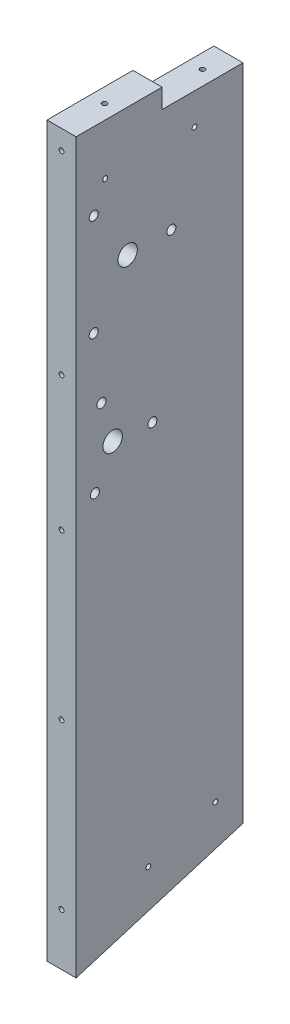
SolidWorks part; units mm, degrees
material "Beech"
ref_plane "Front Plane" through (0, 0, 0) normal (0, 0, 1) x (1, 0, 0)
ref_plane "Top Plane" through (0, 0, 0) normal (0, 1, 0) x (1, 0, 0)
ref_plane "Right Plane" through (0, 0, 0) normal (1, 0, 0) x (0, 0, -1)
sketch "Sketch1" plane through (0, 0, 0) normal (0, 0, 1) x (1, 0, 0)
  line L0 (-331.7795, -427.3421) -> (-331.7795, 0) construction
  line L1 (93.2955, -427.3421) -> (-341.3045, -427.3421) construction
  line L3 (-322.2545, -427.3421) -> (-322.2545, 0)
  line L4 (-341.3045, -427.3421) -> (-341.3045, 0)
  line L5 (-322.2545, -427.3421) -> (-341.3045, -427.3421)
  line L6 (-322.2545, 0) -> (-341.3045, 0)
  line L7 (-341.3045, -427.3421) -> (-341.3045, 12.7) construction
  line L8 (-331.7795, -427.3421) -> (-331.7795, 0) construction
  dimension "D1" = 19.05
extrude "Boss-Extrude1" add sketch "Sketch1" along normal up to surface (53 mm away)
sketch "Sketch2" plane through (0, 0, 53) normal (0, 0, 1) x (1, 0, 0)
  line L0 (-231.3045, 12.7) -> (-341.3045, 12.7) construction
  line L1 (-322.2545, 12.7) -> (-341.3045, 12.7)
  line L4 (-341.3045, 0) -> (-341.3045, -427.3421)
  line L5 (-341.3045, -427.3421) -> (-322.2545, -427.3421)
  line L6 (-322.2545, -427.3421) -> (-322.2545, 0)
  line L7 (-322.2545, 0) -> (-341.3045, 0)
  line L8 (-341.3045, 12.7) -> (-341.3045, -427.3421)
  line L9 (-341.3045, -427.3421) -> (-322.2545, -427.3421)
  line L10 (-322.2545, -427.3421) -> (-322.2545, 12.7)
  dimension "D1" = 0
extrude "Boss-Extrude2" add sketch "Sketch2" along normal up to surface (56.3 mm away)
sketch "Sketch3" plane through (-341.3045, 0, 0) normal (-1, 0, 0) x (0, 0, 1)
  line L0 (0, -427.3421) -> (109.3, -427.3421)
  line L1 (109.3, -427.3421) -> (109.3, -464.2661)
  line L2 (109.3, -464.2661) -> (0, -431.1858)
  line L3 (-12.7, -427.3421) -> (522.1409, -589.2145) construction
  line L4 (0, -431.1858) -> (0, -427.3421)
extrude "Boss-Extrude3" add sketch "Sketch3" against normal through all
hole_wizard "15/64 (0.23438) Diameter Hole1" positions "Sketch5" profile "Sketch6" hole size "15/64" standard "ANSI Inch" end condition through all
sketch "Sketch5" plane through (-341.3045, 0, 0) normal (-1, 0, 0) x (0, 0, 1)
  point P0 (97.7483, -37.836)
  point P3 (97.7483, -104.511)
  point P6 (46.9483, -71.1735)
  point P9 (92.6826, -146.5881)
  point P12 (96.9737, -195.6358)
  point P15 (59.3512, -174.2158)
sketch "Sketch6" plane through (-341.3045, -37.836, 97.7483) normal (0, 1, 0) x (0, 0, 1)
  line L0 (0, 0) -> (0, 19.05)
  line L1 (0, 19.05) -> (2.9766, 19.05)
  line L2 (2.9766, 19.05) -> (2.9766, 0)
  line L5 (2.9766, 0) -> (0, 0)
  line L11 (0, -6.35) -> (0, 107.95) construction
  dimension "Thru Hole Dia." = 5.9533
  dimension "Thru Hole Depth" = 19.05
sketch "Sketch4" plane through (-341.3045, 0, 0) normal (-1, 0, 0) x (0, 0, 1)
  circle A0 centre (75.5233, -71.1735) radius 6.35 construction
  circle A1 centre (75.5233, -71.1735) radius 6.35
  circle A2 centre (85.3394, -171.9421) radius 6.35 construction
  circle A3 centre (85.3394, -171.9421) radius 6.35
extrude "Cut-Extrude1" cut sketch "Sketch4" against normal through all
hole_wizard "Hole1" positions "Sketch7" profile "Sketch8" legacy
sketch "Sketch7" plane through (-124.0045, 10.4243, 122) normal (0, 0, 1) x (-1, 0, 0)
  line L1 (0, 465.9538) -> (0, 167.7243) construction
  point P1 (113.65, 128.8076)
  point P3 (113.65, 23.941)
  point P5 (-94.6, 161.3743)
  point P7 (94.6, 161.3743)
  point P9 (0, 161.3743)
  point P11 (0, 193.1243)
  point P13 (0, 440.5538)
  point P15 (0, 301.9704)
  point P17 (40.9792, 301.9704)
  point P19 (166.7958, 301.9704)
  point P21 (207.775, 440.5538)
  point P23 (207.775, 333.0214)
  point P25 (207.775, 225.489)
  point P27 (207.775, 137.4243)
  point P29 (207.775, 10.4243)
  point P33 (-207.775, 10.4243)
  point P34 (-207.775, 137.4243)
  point P35 (-207.775, 225.489)
  point P36 (-207.775, 333.0214)
  point P37 (-207.775, 440.5538)
  point P38 (-166.7958, 301.9704)
  point P39 (-40.9792, 301.9704)
  point P40 (-113.65, 23.941)
  point P41 (-113.65, 128.8076)
sketch "Sketch8" plane through (-237.6545, -118.3833, 122) normal (1, 0, 0) x (0, -1, 0)
  line L0 (0, 0) -> (0, 32.7039)
  line L1 (0, 32.7039) -> (1.5875, 31.75)
  line L2 (1.5875, 31.75) -> (1.5875, 4.0177)
  line L3 (1.5875, 4.0177) -> (5.08, 0)
  line L4 (5.08, 0) -> (0, 0)
  line L5 (0, -14.3089) -> (0, 102.4216) construction
  line L6 (0, 32.7039) -> (-1.5875, 31.75) construction
  line L7 (-1.5875, 4.0177) -> (-5.08, 0) construction
  dimension "Diameter" = 3.175
  dimension "Depth" = 31.75
  dimension "C-Sink Diameter" = 10.16
  dimension "C-Sink Angle" = 82
  dimension "Drill Angle" = 118
hole_wizard "Hole" positions "Sketch9" profile "Sketch10" legacy
sketch "Sketch9" plane through (-124.0045, 25.4, -155.2867) normal (0, 1, 0) x (-1, 0, 0)
  point P0 (113.65, 236.4367)
  point P2 (207.775, 236.4367)
sketch "Sketch10" plane through (-237.6545, 25.4, 81.15) normal (1, 0, 0) x (0, 0, 1)
  line L0 (0, 0) -> (0, 32.7039)
  line L1 (0, 32.7039) -> (1.5875, 31.75)
  line L2 (1.5875, 31.75) -> (1.5875, 4.0177)
  line L3 (1.5875, 4.0177) -> (5.08, 0)
  line L4 (5.08, 0) -> (0, 0)
  line L5 (0, -14.3089) -> (0, 102.4216) construction
  line L6 (0, 32.7039) -> (-1.5875, 31.75) construction
  line L7 (-1.5875, 4.0177) -> (-5.08, 0) construction
  dimension "Diameter" = 3.175
  dimension "Depth" = 31.75
  dimension "C-Sink Diameter" = 10.16
  dimension "C-Sink Angle" = 82
  dimension "Drill Angle" = 118
hole_wizard "Hole3" positions "Sketch12" profile "Sketch13" legacy
sketch "Sketch12" plane through (-124.0045, 12.7, -155.2867) normal (0, 1, 0) x (-1, 0, 0)
  line L0 (120, 172.2617) -> (217.3, 172.2617) construction
  point P8 (126.35, 172.2617)
  point P10 (207.775, 172.2617)
sketch "Sketch13" plane through (-331.7795, 12.7, 16.975) normal (1, 0, 0) x (0, 0, 1)
  line L0 (0, 0) -> (0, 32.7039)
  line L1 (0, 32.7039) -> (1.5875, 31.75)
  line L2 (1.5875, 31.75) -> (1.5875, 4.0177)
  line L3 (1.5875, 4.0177) -> (5.08, 0)
  line L4 (5.08, 0) -> (0, 0)
  line L5 (0, -14.3089) -> (0, 102.4216) construction
  line L6 (0, 32.7039) -> (-1.5875, 31.75) construction
  line L7 (-1.5875, 4.0177) -> (-5.08, 0) construction
  dimension "Diameter" = 3.175
  dimension "Depth" = 31.75
  dimension "C-Sink Diameter" = 10.16
  dimension "C-Sink Angle" = 82
  dimension "Drill Angle" = 118
hole_wizard "Hole4" positions "Sketch14" profile "Sketch15" legacy
sketch "Sketch14" plane through (-124.0045, 10.4243, -12.7) normal (0, 0, -1) x (1, 0, 0)
  line L12 (0, 0) -> (0, 155.0243) construction
  point P0 (-207.775, 333.0214)
  point P3 (-207.775, 225.489)
  point P6 (-207.775, 137.4243)
  point P9 (-172.1667, 4.0743)
  point P12 (-146.0833, 4.0743)
  point P15 (-94.6, 161.3743)
  point P18 (0, 161.3743)
  point P21 (94.6, 161.3743)
  point P24 (146.0833, 4.0743)
  point P27 (172.1667, 4.0743)
  point P30 (207.775, 137.4243)
  point P33 (207.775, 225.489)
  point P36 (207.775, 333.0214)
  point P39 (166.7958, 301.9704)
  point P42 (40.9792, 301.9704)
  point P45 (-40.9792, 301.9704)
  point P48 (-166.7958, 301.9704)
  point P51 (0, 193.1243)
  point P54 (0, 301.9704)
  point P57 (0, 412.3664)
  point P80 (-126.35, 106.8243)
  point P82 (-126.35, 58.6243)
  point P96 (126.35, 58.6243)
  point P97 (126.35, 106.8243)
sketch "Sketch15" plane through (-331.7795, -322.5971, -12.7) normal (1, 0, 0) x (0, 1, 0)
  line L0 (0, 0) -> (0, 32.7039)
  line L1 (0, 32.7039) -> (1.5875, 31.75)
  line L2 (1.5875, 31.75) -> (1.5875, 4.0177)
  line L3 (1.5875, 4.0177) -> (5.08, 0)
  line L4 (5.08, 0) -> (0, 0)
  line L5 (0, -14.3089) -> (0, 102.4216) construction
  line L6 (0, 32.7039) -> (-1.5875, 31.75) construction
  line L7 (-1.5875, 4.0177) -> (-5.08, 0) construction
  dimension "Diameter" = 3.175
  dimension "Depth" = 31.75
  dimension "C-Sink Diameter" = 10.16
  dimension "C-Sink Angle" = 82
  dimension "Drill Angle" = 118
hole_wizard "Hole5" positions "Sketch16" profile "Sketch17" legacy
sketch "Sketch16" plane through (-124.0045, -363.2296, -268.3751) normal (0, -0.9571, -0.2897) x (1, 0, 0)
  line L4 (-207.775, 822.0847) -> (-207.775, 404.0189) construction
  line L8 (-207.775, 822.0847) -> (-207.775, 717.5683)
  line L9 (-207.775, 717.5683) -> (-207.775, 613.0518)
  line L10 (-207.775, 613.0518) -> (-207.775, 508.5353)
  line L11 (-207.775, 508.5353) -> (-207.775, 404.0189)
  line L12 (-108.65, 822.0847) -> (-108.65, 404.0189) construction
  line L15 (0, 822.0847) -> (0, 613.0518) construction
  line L18 (-207.775, 390.7499) -> (-207.775, 276.5537) construction
  line L22 (-207.775, 390.7499) -> (-207.775, 362.2009)
  line L23 (-207.775, 362.2009) -> (-207.775, 333.6518)
  line L24 (-207.775, 333.6518) -> (-207.775, 305.1027)
  line L25 (-207.775, 305.1027) -> (-207.775, 276.5537)
  line L26 (0, 390.7499) -> (0, 276.5537) construction
  line L30 (0, 276.5537) -> (0, 305.1027)
  line L31 (0, 305.1027) -> (0, 333.6518)
  line L32 (0, 333.6518) -> (0, 362.2009)
  line L33 (0, 362.2009) -> (0, 390.7499)
  point P24 (-207.775, 613.0518)
  point P31 (-207.775, 456.2771)
  point P33 (-207.775, 769.8265)
  point P52 (-108.65, 456.2771)
  point P54 (-108.65, 630.1265)
  point P56 (-108.65, 769.8265)
  point P76 (-207.775, 362.2009)
  point P80 (-207.775, 305.1027)
  point P99 (0, 305.1027)
  point P104 (0, 362.2009)
  point P113 (207.775, 305.1027)
  point P114 (207.775, 362.2009)
  point P115 (108.65, 769.8265)
  point P116 (108.65, 630.1265)
  point P117 (108.65, 456.2771)
  point P118 (207.775, 769.8265)
  point P119 (207.775, 456.2771)
  point P120 (207.775, 613.0518)
  dimension "D1" = 139.7
sketch "Sketch17" plane through (83.7705, -540.8176, 318.3915) normal (1, 0, 0) x (0, 0.2897, -0.9571)
  line L0 (0, 0) -> (0, 32.7039)
  line L1 (0, 32.7039) -> (1.5875, 31.75)
  line L2 (1.5875, 31.75) -> (1.5875, 4.0177)
  line L3 (1.5875, 4.0177) -> (5.08, 0)
  line L4 (5.08, 0) -> (0, 0)
  line L5 (0, -14.3089) -> (0, 102.4216) construction
  line L6 (0, 32.7039) -> (-1.5875, 31.75) construction
  line L7 (-1.5875, 4.0177) -> (-5.08, 0) construction
  dimension "Diameter" = 3.175
  dimension "Depth" = 31.75
  dimension "C-Sink Diameter" = 10.16
  dimension "C-Sink Angle" = 82
  dimension "Drill Angle" = 118
hole_wizard "Hole6" positions "Sketch18" profile "Sketch19" legacy
sketch "Sketch18" plane through (-354.0045, 10.4243, -155.2867) normal (-1, 0, 0) x (0, -0.9959, 0.09)
  line L0 (54.6742, 260.7254) -> (44.8416, 151.8686) construction
  line L6 (458.2175, 188.8136) -> (426.7882, 117.3689) construction
  line L11 (443.4217, 288.0956) -> (513.4071, 262.4897) construction
  line L16 (479.186, 443.3317) -> (498.5551, 428.1819) construction
  line L19 (643.2075, 626.7743) -> (602.3132, 525.5573) construction
  line L24 (664.0363, 618.3589) -> (454.7061, 100.2486) construction
  line L28 (664.0363, 618.3589) -> (611.7037, 488.8313)
  line L29 (611.7037, 488.8313) -> (559.3712, 359.3037)
  line L30 (559.3712, 359.3037) -> (507.0387, 229.7761)
  line L31 (507.0387, 229.7761) -> (454.7061, 100.2486)
  point P12 (52.9605, 241.7526)
  point P14 (47.6978, 183.4898)
  point P29 (434.4591, 134.8062)
  point P31 (453.1036, 177.1887)
  point P48 (478.4144, 275.2927)
  point P60 (488.8705, 435.7568)
  point P79 (636.0712, 609.1114)
  point P81 (609.4494, 543.2202)
  point P98 (559.3712, 359.3037)
  point P100 (507.0387, 229.7761)
  point P112 (637.87, 553.5951)
sketch "Sketch19" plane through (-354.0045, -575.0582, 453.4463) normal (0, 1, 0) x (0, 0, 1)
  line L0 (0, 0) -> (0, 32.7039)
  line L1 (0, 32.7039) -> (1.5875, 31.75)
  line L2 (1.5875, 31.75) -> (1.5875, 4.0177)
  line L3 (1.5875, 4.0177) -> (5.08, 0)
  line L4 (5.08, 0) -> (0, 0)
  line L5 (0, -14.3089) -> (0, 102.4216) construction
  line L6 (0, 32.7039) -> (-1.5875, 31.75) construction
  line L7 (-1.5875, 4.0177) -> (-5.08, 0) construction
  dimension "Diameter" = 3.175
  dimension "Depth" = 31.75
  dimension "C-Sink Diameter" = 10.16
  dimension "C-Sink Angle" = 82
  dimension "Drill Angle" = 118
